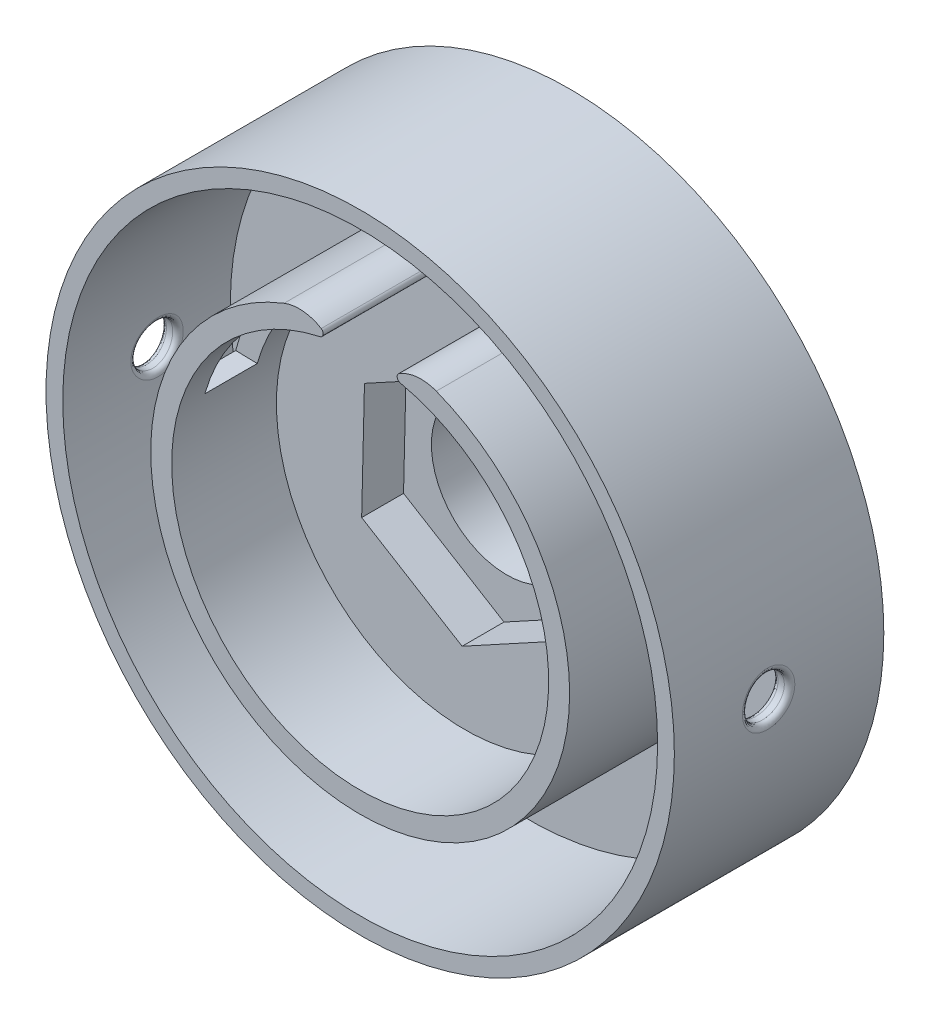
SolidWorks part; units mm, degrees
ref_plane "Front Plane" through (0, 0, 0) normal (0, 0, 1) x (1, 0, 0)
ref_plane "Top Plane" through (0, 0, 0) normal (0, 1, 0) x (1, 0, 0)
ref_plane "Right Plane" through (0, 0, 0) normal (1, 0, 0) x (0, 0, -1)
sketch "Sketch1" plane through (0, 0, 0) normal (0, 0, 1) x (1, 0, 0)
  circle A0 centre (0, 0) radius 15
extrude "Boss-Extrude1" add sketch "Sketch1" along normal blind 10
sketch "Sketch2" plane through (0, 0, 10) normal (0, 0, 1) x (1, 0, 0)
  circle A0 centre (0, 0) radius 3.6
extrude "Cut-Extrude1" cut sketch "Sketch2" against normal through all
sketch "Sketch3" plane through (0, 0, 10) normal (0, 0, 1) x (1, 0, 0)
  circle A0 centre (0, 0) radius 9
extrude "Cut-Extrude2" cut sketch "Sketch3" against normal blind 5
sketch "Sketch4" plane through (0, 0, 5) normal (0, 0, 1) x (1, 0, 0)
  line L1 (4.7958, -2.9234) -> (4.9296, 2.6916)
  line L2 (4.9296, 2.6916) -> (0.1338, 5.615)
  line L3 (0.1338, 5.615) -> (-4.7958, 2.9234)
  line L4 (-4.7958, 2.9234) -> (-4.9296, -2.6916)
  line L5 (-4.9296, -2.6916) -> (-0.1338, -5.615)
  line L6 (-0.1338, -5.615) -> (4.7958, -2.9234)
  circle A0 centre (0, 0) radius 4.8641 construction
  dimension "D1" = 11.23
extrude "Cut-Extrude3" cut sketch "Sketch4" against normal blind 2
sketch "Sketch5" plane through (0, 0, 10) normal (0, 0, 1) x (1, 0, 0)
  circle A0 centre (0, 0) radius 10
  circle A1 centre (0, 0) radius 14.2
extrude "Cut-Extrude4" cut sketch "Sketch5" against normal blind 8
sketch "Sketch6" plane through (0, 0, 10) normal (0, 0, 1) x (1, 0, 0)
  circle A0 centre (0, 0) radius 15
  circle A1 centre (0, 0) radius 14.5
sketch "Sketch7" plane through (0, 0, 10) normal (0, 0, 1) x (1, 0, 0)
  line L1 (-1.5, 12.2356) -> (1.5, 12.2356)
  line L2 (-1.5, 12.2356) -> (-1.5, 8.8741)
  line L3 (-1.5, 8.8741) -> (1.5, 8.8741)
  line L4 (1.5, 12.2356) -> (1.5, 8.8741)
  circle A0 centre (0, 0) radius 9 construction
  dimension "D1" = 3
  dimension "D2" = 1.5
extrude "Cut-Extrude6" cut sketch "Sketch7" against normal blind 5
fillet "Fillet2" radius 2 2 edges at (-1.5, 9.8869, 7.5) (1.5, 9.8869, 7.5)
fillet "Fillet3" radius 0.2 2 edges at (1.5, 8.8741, 7.5) (-1.5, 8.8741, 7.5)
sketch "Sketch8" plane through (0, 0, 0) normal (0, 0, -1) x (-1, 0, 0)
  line L1 (-2.2, -5.95) -> (2.2, -5.95)
  line L2 (-2.2, -5.95) -> (-2.2, -8.35)
  line L3 (-2.2, -8.35) -> (2.2, -8.35)
  line L4 (2.2, -5.95) -> (2.2, -8.35)
  dimension "D1" = 2.2
  dimension "D2" = 5.95
  dimension "D3" = 2.4
  dimension "D4" = 4.4
extrude "Cut-Extrude7" cut sketch "Sketch8" against normal blind 3
sketch "Sketch9" plane through (4.8627, -0.1159, 0) normal (-0.9997, 0.0238, 0) x (0, 0, 1)
  line L0 (10, -10) -> (10, 9.4002) construction
  line L1 (6.25, 6.2271) -> (8.75, 6.2271)
  line L2 (6.25, 6.2271) -> (6.25, 2.2271)
  line L3 (6.25, 2.2271) -> (8.75, 2.2271)
  line L4 (8.75, 6.2271) -> (8.75, 2.2271)
  line L5 (10, 9.2271) -> (5, 9.2271) construction
  dimension "D1" = 1.25
  dimension "D2" = 3
  dimension "D3" = 2.5
  dimension "D4" = 4
extrude "Cut-Extrude8" cut sketch "Sketch9" along normal blind 15
ref_plane "Plane1" through (15, 0, 0) normal (1, 0, 0) x (0, 0, -1)
sketch "Sketch10" plane through (15, 0, 0) normal (1, 0, 0) x (0, 0, -1)
  line L0 (0, 15) -> (-10, 15) construction
  line L1 (0, -15) -> (0, 15) construction
  circle A0 centre (-5.5, 0) radius 1
  dimension "D1" = 15
  dimension "D2" = 5.5
extrude "Cut-Extrude9" cut sketch "Sketch10" against normal up to next
fillet "Fillet6" radius 0.25 2 edges at (14.9983, -0.2275, 6.4738) (14.1982, 0.2272, 6.4738)
ref_plane "Plane2" through (-15, 0, 0) normal (1, 0, 0) x (0, 0, -1)
sketch "Sketch12" plane through (-15, 0, 0) normal (1, 0, 0) x (0, 0, -1)
  line L0 (0, -15) -> (0, 15) construction
  line L1 (0, 15) -> (-10, 15) construction
  circle A0 centre (-5.5, 0) radius 1
  dimension "D1" = 5.5
  dimension "D2" = 15
extrude "Cut-Extrude11" cut sketch "Sketch12" along normal up to next
fillet "Fillet7" radius 0.25 2 edges at (-14.1982, -0.2272, 4.5262) (-14.9983, 0.2275, 4.5262)
